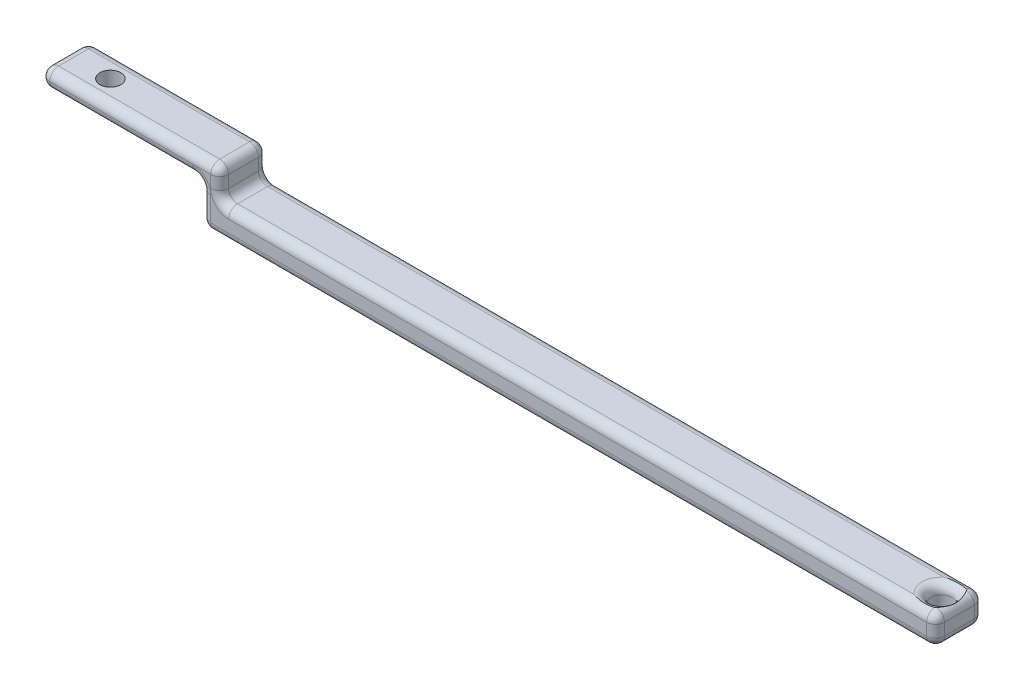
SolidWorks part; units mm, degrees
ref_plane "Front Plane" through (0, 0, 0) normal (0, 0, 1) x (1, 0, 0)
ref_plane "Top Plane" through (0, 0, 0) normal (0, 1, 0) x (1, 0, 0)
ref_plane "Right Plane" through (0, 0, 0) normal (1, 0, 0) x (0, 0, -1)
sketch "Sketch1" plane through (0, 0, 0) normal (0, 0, 1) x (1, 0, 0)
  line L0 (0, 0) -> (-33417.0761, 0) construction
  line L1 (-58.9676, 7.5) -> (-28.9676, 7.5)
  line L2 (-28.9676, 7.5) -> (-28.9676, 2.5)
  line L3 (-28.9676, 2.5) -> (91.0324, 2.5)
  line L4 (91.0324, 2.5) -> (91.0324, -2.5)
  line L5 (91.0324, -2.5) -> (-31.9676, -2.5)
  line L6 (-31.9676, -2.5) -> (-31.9676, 4.5)
  line L7 (-31.9676, 4.5) -> (-58.9676, 4.5)
  line L8 (-58.9676, 4.5) -> (-58.9676, 7.5)
  point P5 (-58.9676, 6)
  dimension "D1" = 5
  dimension "D2" = 2.5
  dimension "D3" = 30
  dimension "D4" = 27
  dimension "D5" = 150
  dimension "D6" = 3
  dimension "D7" = 10
extrude "Boss-Extrude2" add sketch "Sketch1" against normal blind 8
sketch "Sketch2" plane through (0, 2.5, 0) normal (0, 1, 0) x (1, 0, 0)
  line L0 (91.0324, 8) -> (91.0324, 0) construction
  line L2 (91.0324, 8) -> (-28.9676, 8) construction
  circle A0 centre (88.0324, 4) radius 1.75
  point P6 (88.2308, 8)
  dimension "D1" = 3.5
  dimension "D2" = 3
  dimension "D3" = 4
extrude "Cut-Extrude1" cut sketch "Sketch2" against normal through all
fillet "Fillet1" radius 1.5 24 edges at (-45.4676, 4.5, -8) (-28.9676, 5, -8) (-43.9676, 7.5, -8) (-28.9676, 7.5, -4) (91.0324, 0, -8) (91.0324, -2.5, -4) (29.5324, -2.5, -8) (86.2824, -2.5, -4) (-58.9676, 4.5, -4) (-58.9676, 7.5, -4) (-31.9676, -2.5, -4) (-31.9676, 1, -8) (-31.9676, 4.5, -4) (-28.9676, 2.5, -4) (31.0324, 2.5, -8) (91.0324, 2.5, -4) (86.2824, 2.5, -4) (-43.9676, 7.5, 0) (-28.9676, 5, 0) (31.0324, 2.5, 0) (91.0324, 0, 0) (29.5324, -2.5, 0) (-31.9676, 1, 0) (-45.4676, 4.5, 0)
sketch "Sketch3" plane through (0, 7.5, 0) normal (0, 1, 0) x (1, 0, 0)
  line L0 (-57.4676, 1.5) -> (-30.4676, 1.5) construction
  circle A0 centre (-51.293, 4) radius 1.75
  dimension "D1" = 3.5
  dimension "D2" = 2.5
extrude "Cut-Extrude2" cut sketch "Sketch3" against normal blind 3
